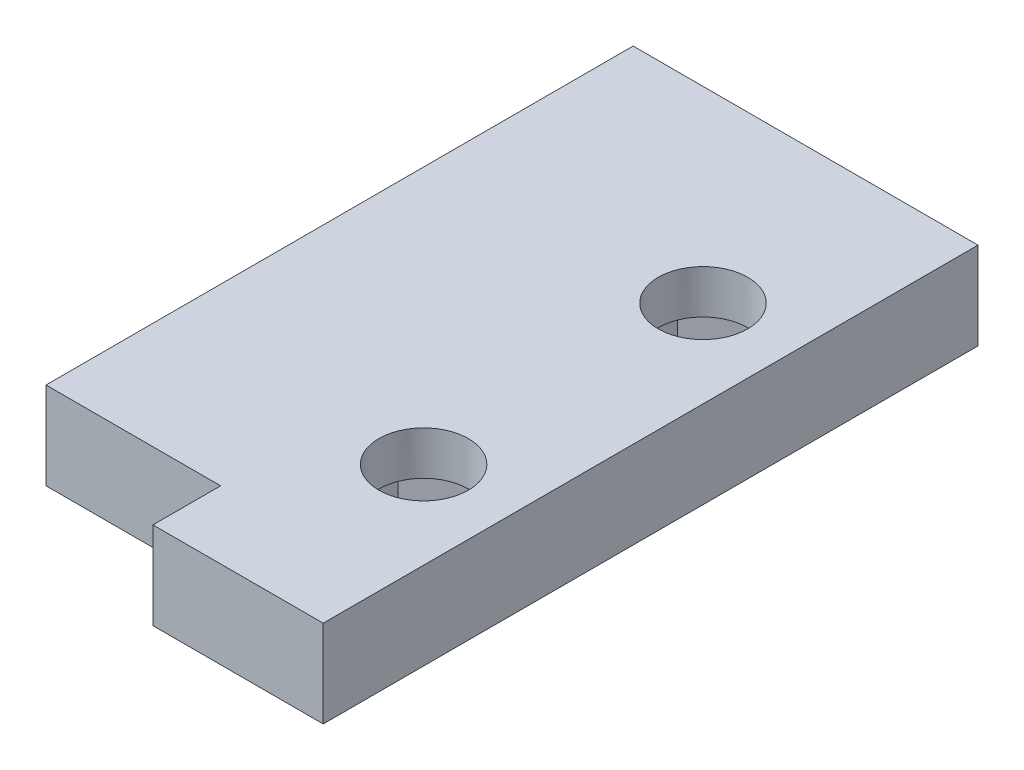
SolidWorks part; units mm, degrees
ref_plane "前视基准面" through (0, 0, 0) normal (0, 0, 1) x (1, 0, 0)
ref_plane "上视基准面" through (0, 0, 0) normal (0, 1, 0) x (1, 0, 0)
ref_plane "右视基准面" through (0, 0, 0) normal (1, 0, 0) x (0, 0, -1)
other "Configuration Table"
sketch "草图1" plane through (0, 0, 0) normal (0, 1, 0) x (1, 0, 0)
  line L1 (0, 0) -> (15.8, 0)
  line L2 (0, 0) -> (0, 30)
  line L3 (0, 30) -> (15.8, 30)
  line L4 (15.8, 0) -> (15.8, 30)
  dimension "D1" = 15.8
  dimension "D2" = 30
extrude "凸台-拉伸1" add sketch "草图1" along normal blind 4
sketch "草图2" plane through (0, 4, 0) normal (0, 1, 0) x (1, 0, 0)
  line L0 (11.8, 30) -> (11.8, 0) construction
  line L3 (0, 15) -> (15.8, 15) construction
  line L16 (0, 30) -> (0, 0) construction
  line L17 (15.8, 0) -> (15.8, 30) construction
  circle A0 centre (11.8, 21.4) radius 2.05
  circle A1 centre (11.8, 8.6) radius 2.05
  dimension "D1" = 4.1
  dimension "D2" = 4.1
  dimension "D3" = 12.8
  dimension "D4" = 4
extrude "切除-拉伸1" cut sketch "草图2" against normal through all
sketch "草图5" plane through (0, 0, 0) normal (0, -1, 0) x (1, 0, 0)
  line L1 (14.55, -7.0123) -> (11.8, -5.4246)
  line L2 (11.8, -5.4246) -> (9.05, -7.0123)
  line L3 (9.05, -7.0123) -> (9.05, -10.1877)
  line L4 (9.05, -10.1877) -> (11.8, -11.7754)
  line L5 (11.8, -11.7754) -> (14.55, -10.1877)
  line L6 (14.55, -10.1877) -> (14.55, -7.0123)
  line L7 (9.05, -22.9877) -> (11.8, -24.5754)
  line L8 (11.8, -24.5754) -> (14.55, -22.9877)
  line L9 (14.55, -22.9877) -> (14.55, -19.8123)
  line L10 (14.55, -19.8123) -> (11.8, -18.2246)
  line L11 (11.8, -18.2246) -> (9.05, -19.8123)
  line L12 (9.05, -19.8123) -> (9.05, -22.9877)
  circle A0 centre (11.8, -8.6) radius 2.75 construction
  circle A1 centre (11.8, -21.4) radius 2.75 construction
  dimension "D1" = 5.5
  dimension "D2" = 5.5
extrude "切除-拉伸2" cut sketch "草图5" against normal blind 2
ref_axis "基准轴1" through (11.8, 2, -21.4) along (0, 1, 0)
ref_axis "基准轴2" through (11.8, 2, -8.6) along (0, 1, 0)
sketch "草图7" plane through (0, 4, 0) normal (0, 1, 0) x (1, 0, 0)
  line L1 (0, 0) -> (8, 0)
  line L2 (0, 0) -> (0, 3.1)
  line L3 (0, 3.1) -> (8, 3.1)
  line L4 (8, 0) -> (8, 3.1)
  dimension "D1" = 3.1
  dimension "D2" = 8
extrude "切除-拉伸3" cut sketch "草图7" against normal up to next
